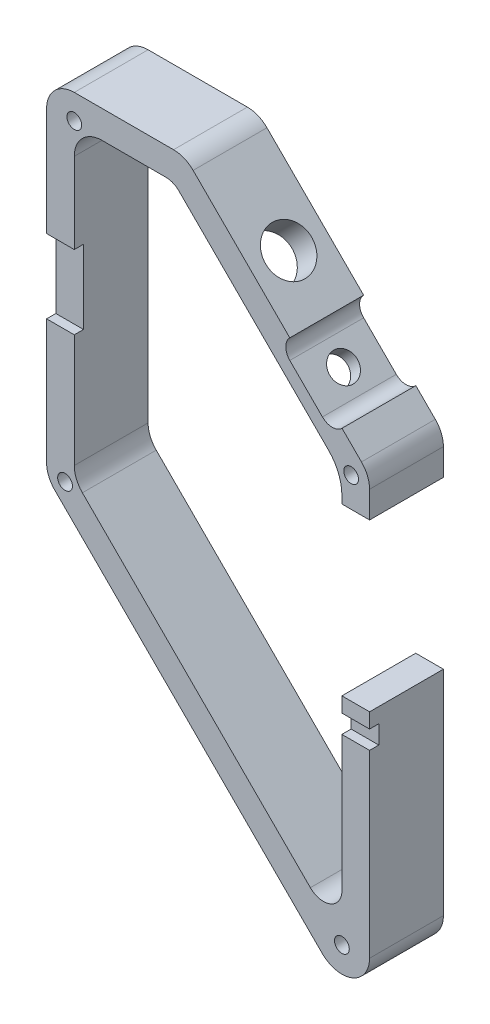
SolidWorks part; units mm, degrees
material "ABS"
ref_plane "Спереди" through (0, 0, 0) normal (0, 0, 1) x (1, 0, 0)
ref_plane "Сверху" through (0, 0, 0) normal (0, 1, 0) x (1, 0, 0)
ref_plane "Справа" through (0, 0, 0) normal (1, 0, 0) x (0, 0, -1)
sketch "Эскиз8" plane through (0, 0, 0) normal (0, 0, 1) x (1, 0, 0)
  line L0 (0, -18.75) -> (0, 18.75)
  line L1 (0, 18.75) -> (15, 18.75)
  line L2 (15, 18.75) -> (35, -1.25)
  line L3 (35, -1.25) -> (35, -53.75)
  line L9 (32, -46.5074) -> (3, -17.5074)
  line L11 (3, 15.75) -> (13.7574, 15.75)
  line L12 (13.7574, 15.75) -> (32, -2.4926)
  line L15 (35, -53.75) -> (0, -18.75) construction
  line L16 (32, -46.5074) -> (3, -17.5074) construction
  line L17 (3, -17.5074) -> (3, 15.75) construction
  line L18 (3, 15.75) -> (3, -17.5074)
  line L20 (32, -2.4926) -> (32, -46.5074)
  line L21 (32, -2.4926) -> (32, -46.5074) construction
  line L24 (0, -18.75) -> (35, -53.75)
  point P0 (0, 0)
  dimension "D1" = 45
  dimension "D2" = 15
  dimension "D3" = 135
  dimension "D4" = 35
  dimension "D5" = 3
  dimension "D6" = 3
  dimension "D7" = 37.5
extrude "База" add sketch "Эскиз8" against normal blind 8
fillet "Скругление4" radius 3 6 edges at (15, 18.75, -4) (35, -1.25, -4) (0, 18.75, -4) (3, 15.75, -4) (3, -17.5074, -4) (0, -18.75, -4)
fillet "Скругление5" radius 2 2 edges at (32, -46.5074, -4) (13.7574, 15.75, -4)
sketch "Эскиз13" plane through (0, 0, 0) normal (0, 0, -1) x (-1, 0, 0)
  line L0 (0, 15.75) -> (0, -17.5074) construction
  line L1 (0, 4) -> (-3, 4)
  line L2 (0, 4) -> (0, -4)
  line L3 (0, -4) -> (-3, -4)
  line L4 (-3, 4) -> (-3, -4)
  line L5 (-3, -16.2647) -> (-3, 12.75) construction
  line L6 (-32, -41.6789) -> (-32, -2.4926) construction
  line L7 (-32, -25) -> (-35, -25)
  line L8 (-32, -25) -> (-32, -27)
  line L9 (-32, -27) -> (-35, -27)
  line L10 (-35, -25) -> (-35, -27)
  line L11 (-35, -53.75) -> (-35, -2.4926) construction
  point P13 (0, 0)
  dimension "D1" = 8
  dimension "D2" = 2
  dimension "D3" = 25
extrude "Вырез проводов" cut sketch "Эскиз13" along normal blind 1
hole_wizard "Крепление рамки M2" positions "Эскиз11" profile "Эскиз12" tap size "M2" standard "DIN" end condition through all
sketch "Эскиз11" plane through (0, 0, 0) normal (0, 0, 1) x (1, 0, 0)
  point P0 (2, -18.3)
  point P28 (3, 16.07)
  point P50 (32, -46.75)
  point P148 (33, -2.17)
  dimension "D1" = 46.75
  dimension "D2" = 32
  dimension "D3" = 16.07
  dimension "D4" = 3
  dimension "D5" = 18.3
  dimension "D6" = 2
  dimension "D7" = 2.17
  dimension "D8" = 33
sketch "Эскиз12" plane through (2, -18.3, 0) normal (1, 0, 0) x (0, -1, 0)
  line L0 (0, 0) -> (0, 8)
  line L1 (0, 8) -> (0.8, 8)
  line L2 (0.8, 8) -> (0.8, 0)
  line L5 (0.8, 0) -> (0, 0)
  line L11 (0, -6.35) -> (0, 107.95) construction
  dimension "Диаметр проходного сверла" = 1.6
  dimension "Глубина проходного сверла" = 8
cosmetic thread "Отверстие резьбы1" parameters "D2"=2
cosmetic thread "Отверстие резьбы2" parameters "D2"=2
cosmetic thread "Отверстие резьбы5" parameters "D2"=2
cosmetic thread "Отверстие резьбы6" parameters "D2"=2
fillet "Скругление6" radius 3 1 edges at (35, -53.75, -4)
fillet "Скругление7" radius 5 1 edges at (32, -2.4926, -4)
sketch "Эскиз19" plane through (0, 0, 0) normal (0, 0, 1) x (1, 0, 0)
  line L0 (35, -25) -> (35, -2.4926) construction
  line L1 (31, -5.38) -> (35, -5.38)
  line L2 (31, -5.38) -> (31, -23.38)
  line L3 (31, -23.38) -> (35, -23.38)
  line L4 (35, -5.38) -> (35, -23.38)
  dimension "D1" = 18
  dimension "D2" = 31
  dimension "D3" = 5.38
extrude "Вырез разъема" cut sketch "Эскиз19" against normal through all
sketch "Эскиз20" plane through (16.875, 16.875, 0) normal (0.7071, 0.7071, 0) x (0, 0, -1)
  line L0 (8, 1.409) -> (0, 1.409) construction
  circle A0 centre (4, -7.571) radius 2.5
  circle A1 centre (4.0519, -17.4075) radius 1.5
  point P5 (4, 1.409)
  dimension "D1" = 5
  dimension "D3" = 3
  dimension "D2" = 8.98
extrude "Вырез-Вытянуть1" cut sketch "Эскиз20" against normal up to next
sketch "Эскиз21" plane through (0, 0, 0) normal (0, 0, 1) x (1, 0, 0)
  line L0 (26.3556, 7.3944) -> (25.2949, 6.3338)
  line L1 (34.1213, -0.3713) -> (15.8787, 17.8713) construction
  line L2 (25.2949, 6.3338) -> (30.9518, 0.6769)
  line L3 (30.9518, 0.6769) -> (32.0124, 1.7376)
  line L4 (32.0124, 1.7376) -> (26.3556, 7.3944)
  line L5 (27.0627, 4.566) -> (29.184, 2.4447) construction
  line L6 (28.1233, 5.6267) -> (26.002, 3.5054) construction
  line L7 (28.1233, 1.384) -> (30.2446, 3.5054) construction
  point P12 (28.1233, 3.5054)
  point P13 (28.1233, 3.5054)
  dimension "D1" = 8
extrude "Вырез-Вытянуть2" cut sketch "Эскиз21" against normal through all
fillet "Скругление8" radius 1.5 2 edges at (30.9518, 0.6769, -4) (25.2949, 6.3338, -4)
